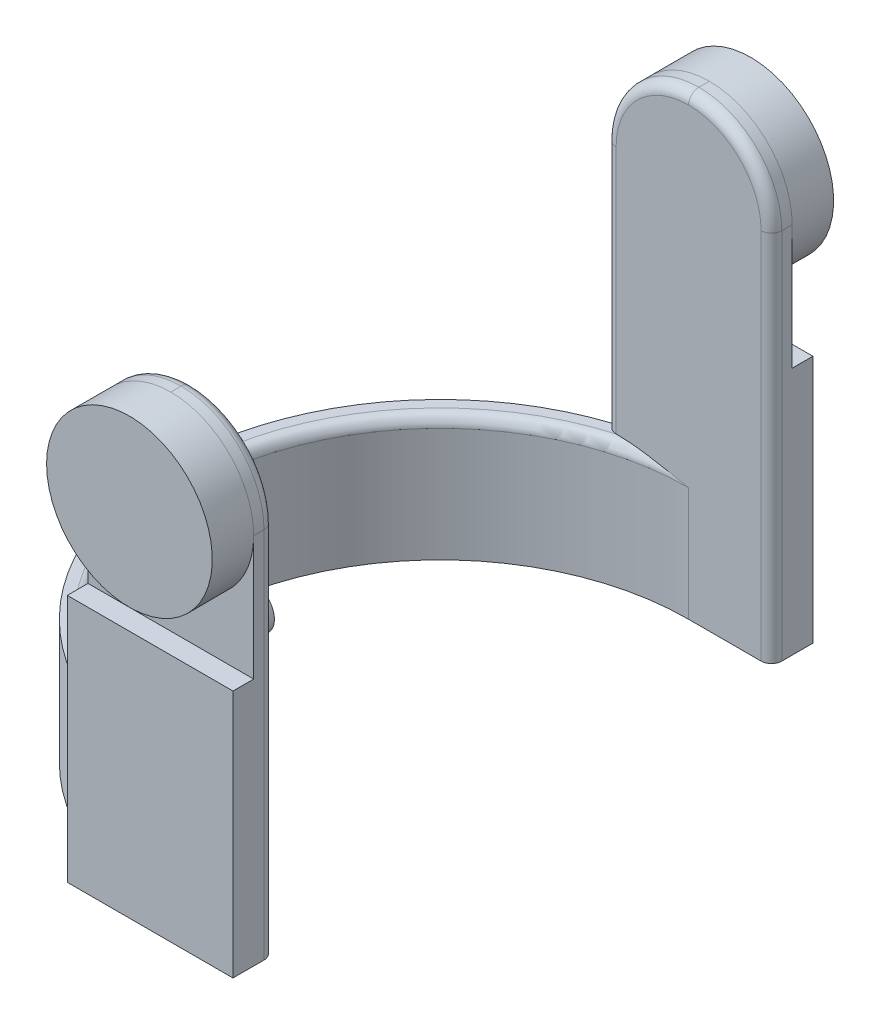
SolidWorks part; units mm, degrees
ref_plane "Front Plane" through (0, 0, 0) normal (0, 0, 1) x (1, 0, 0)
ref_plane "Top Plane" through (0, 0, 0) normal (0, 1, 0) x (1, 0, 0)
ref_plane "Right Plane" through (0, 0, 0) normal (1, 0, 0) x (0, 0, -1)
sketch "Sketch1" plane through (0, 0, 0) normal (0, 1, 0) x (1, 0, 0)
  line L0 (0, 65) -> (0, 60)
  line L1 (0, -60) -> (0, -65)
  arc A0 (0, 60) -> (0, -60) centre (0, 0) ccw
  arc A1 (0, -65) -> (0, 65) centre (0, 0) cw
  dimension "D1" = 60
  dimension "D2" = 65
extrude "Boss-Extrude1" add sketch "Sketch1" along normal blind 30
sketch "Sketch2" plane through (0, 0, 0) normal (0, 1, 0) x (1, 0, 0)
  line L0 (0, 60) -> (0, 65) construction
  line L1 (20, 60) -> (-20, 60)
  line L2 (20, 60) -> (20, 70)
  line L3 (20, 70) -> (-20, 70)
  line L4 (-20, 60) -> (-20, 70)
  line L5 (0, 60) -> (0, 65) construction
  point P6 (0, 62.5)
  dimension "D1" = 40
  dimension "D2" = 10
  dimension "D3" = 20
  dimension "D4" = 7.5
extrude "Boss-Extrude2" add sketch "Sketch2" along normal blind 110
sketch "Sketch3" plane through (0, 110, 0) normal (0, 1, 0) x (1, 0, 0)
  line L0 (-20, 70) -> (-20, 60) construction
  line L1 (20, 70) -> (-20, 70)
  line L2 (20, 70) -> (20, 65)
  line L3 (20, 65) -> (-20, 65)
  line L4 (-20, 70) -> (-20, 65)
extrude "Cut-Extrude1" cut sketch "Sketch3" against normal blind 50
sketch "Sketch4" plane through (0, 0, -65) normal (0, 0, -1) x (-1, 0, 0)
  circle A0 centre (0, 90) radius 20
  dimension "D1" = 40
extrude "Boss-Extrude4" add sketch "Sketch4" along normal blind 10
fillet "Fillet1" radius 20 2 edges at (20, 110, -62.5) (-20, 110, -62.5)
mirror "Mirror1" about plane through (0, 0, 0) normal (0, 0, 1) of "Fillet1", "Boss-Extrude4", "Boss-Extrude2", "Cut-Extrude1"
sketch "Sketch5" plane through (0, 0, 0) normal (0, -1, 0) x (1, 0, 0)
  line L1 (-60, -10) -> (-70, -10)
  line L2 (-60, -10) -> (-60, 10)
  line L3 (-60, 10) -> (-70, 10)
  line L4 (-70, -10) -> (-70, 10)
  arc A0 (-20, 61.8466) -> (-20, -61.8466) centre (0, 0) ccw construction
  point P4 (-65, 0)
  point P8 (-65, 0)
  dimension "D1" = 20
  dimension "D2" = 10
  dimension "D3" = 10
  dimension "D4" = 5
extrude "Boss-Extrude5" add sketch "Sketch5" along normal blind 10 and the other way blind 30
sketch "Sketch6" plane through (0, 0, 0) normal (0, 0, 1) x (1, 0, 0)
  line L0 (-60, -10) -> (-70, -10) construction
  circle A0 centre (-65, -10) radius 5
extrude "Boss-Extrude6" add sketch "Sketch6" along normal blind 20 and the other way blind 20
fillet "Fillet2" radius 2.5 9 edges at (-20, 60, 60) (-14.1421, 104.1421, 60) (14.1421, 104.1421, 60) (-20, 60, -60) (-14.1421, 104.1421, -60) (14.1421, 104.1421, -60) (20, 45, 60) (20, 45, -60) (-60, 30, 0)
